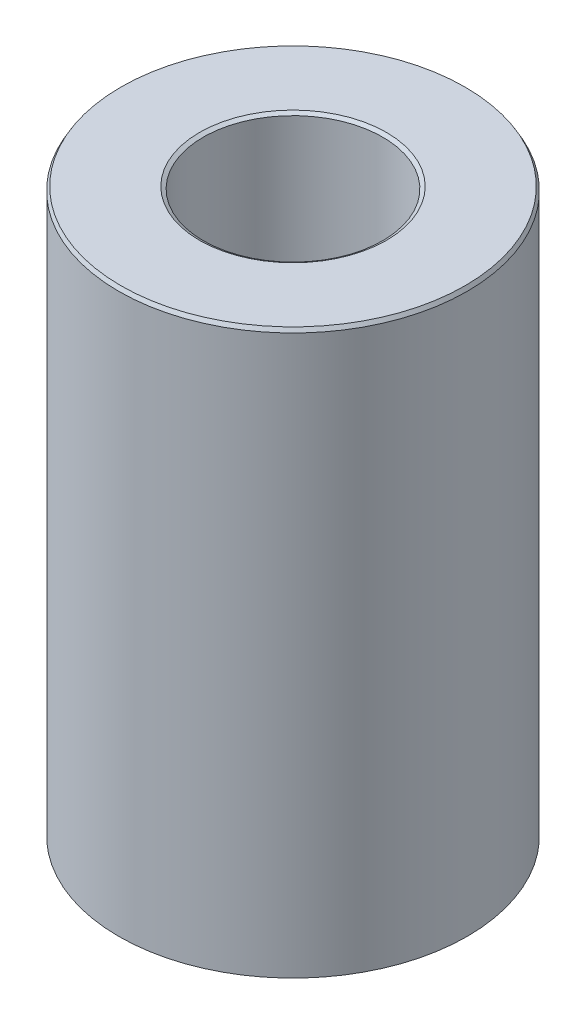
SolidWorks part; units mm, degrees
ref_plane "Front Plane" through (0, 0, 0) normal (0, 0, 1) x (1, 0, 0)
ref_plane "Top Plane" through (0, 0, 0) normal (0, 1, 0) x (1, 0, 0)
ref_plane "Right Plane" through (0, 0, 0) normal (1, 0, 0) x (0, 0, -1)
sketch "Sketch1" plane through (0, 0, 0) normal (0, 1, 0) x (1, 0, 0)
  circle A0 centre (0, 0) radius 57.5
  dimension "SLEEVE_OD" = 115
extrude "Boss-Extrude1" add sketch "Sketch1" along normal blind 186.3076
sketch "Sketch2" plane through (0, 0, 0) normal (0, 1, 0) x (1, 0, 0)
  circle A0 centre (0, 0) radius 29.6105
  dimension "BORE_D" = 59.221
extrude "Cut-Extrude1" cut sketch "Sketch2" along normal through all
chamfer "Chamfer1" distance 1.2408 angle 30 4 edges at (0, 186.3076, 29.6105) (0, 0, 29.6105) (0, 0, 57.5) (0, 186.3076, 57.5) first distance on face at (0, 186.3076, 29.6105) first distance on face at (0, 0, 29.6105) first distance on face at (0, 186.3076, 57.5)
